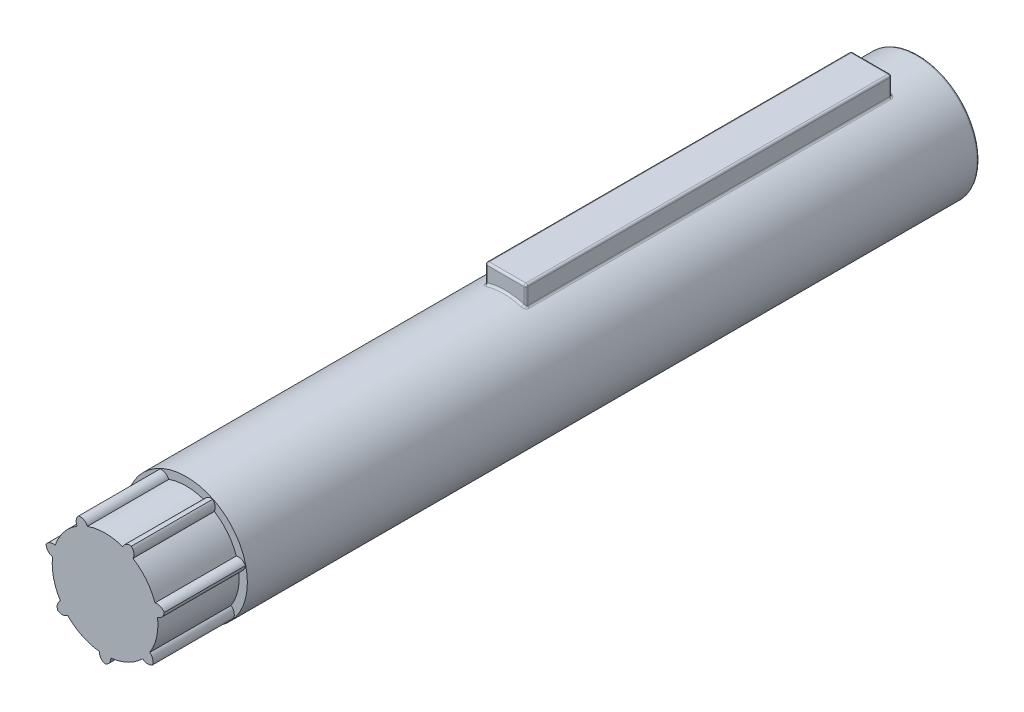
SolidWorks part; units mm, degrees
ref_plane "Front Plane" through (0, 0, 0) normal (0, 0, 1) x (1, 0, 0)
ref_plane "Top Plane" through (0, 0, 0) normal (0, 1, 0) x (1, 0, 0)
ref_plane "Right Plane" through (0, 0, 0) normal (1, 0, 0) x (0, 0, -1)
sketch "Sketch1" plane through (0, 0, 0) normal (0, 0, 1) x (1, 0, 0)
  circle A1 centre (0, 0) radius 7.5
  dimension "D1" = 15
extrude "Boss-Extrude1" add sketch "Sketch1" along normal blind 100
sketch "Sketch2" plane through (0, 0, 0) normal (0, 1, 0) x (1, 0, 0)
  line L0 (7.5, 0) -> (-7.5, 0) construction
  line L1 (-2.5, -5.75) -> (2.5, -5.75)
  line L2 (-2.5, -5.75) -> (-2.5, -50.75)
  line L3 (-2.5, -50.75) -> (2.5, -50.75)
  line L4 (2.5, -5.75) -> (2.5, -50.75)
  line L5 (-2.5, -5.75) -> (2.5, -50.75) construction
  line L6 (-2.5, -50.75) -> (2.5, -5.75) construction
  point P0 (0, -28.25)
  point P5 (0, 0)
  dimension "D1" = 45
  dimension "D2" = 5
  dimension "D3" = 5.75
extrude "Boss-Extrude3" add sketch "Sketch2" along normal blind 9.5 contours L2 L1 L4 L3
sketch "Sketch3" plane through (0, 0, 100) normal (0, 0, 1) x (1, 0, 0)
  line L0 (-2.5, 7.0711) -> (0, 0)
  line L1 (0, 0) -> (2.5, 7.0711)
  circle A2 centre (0, 0) radius 6.5
  circle A3 centre (0, 0) radius 6.5
  circle M2 centre (0, 0) radius 7.5
  dimension "D1" = 1
extrude "Cut-Extrude1" cut sketch "Sketch3" against normal blind 10 contours A3 L1 L0 M2
fillet "Fillet1" radius 1 2 edges at (2.5, 7.0711, 95) (-2.5, 7.0711, 95)
pattern_circular "CirPattern8" count 7 over 360 about axis through (0, 0, 0) along (0, 0, 1) of "Fillet1", "Cut-Extrude1"
fillet "Fillet3" radius 0.25 13 edges at (0, 7.5, 50.75) (0, 7.5, 5.75) (7.5, 0, 0) (-2.5, 8.2855, 50.75) (-2.5, 7.0711, 28.25) (-2.5, 8.2855, 5.75) (2.5, 8.2855, 50.75) (2.5, 8.2855, 5.75) (2.5, 7.0711, 28.25) (-2.5, 9.5, 28.25) (0, 9.5, 5.75) (2.5, 9.5, 28.25) (0, 9.5, 50.75)
